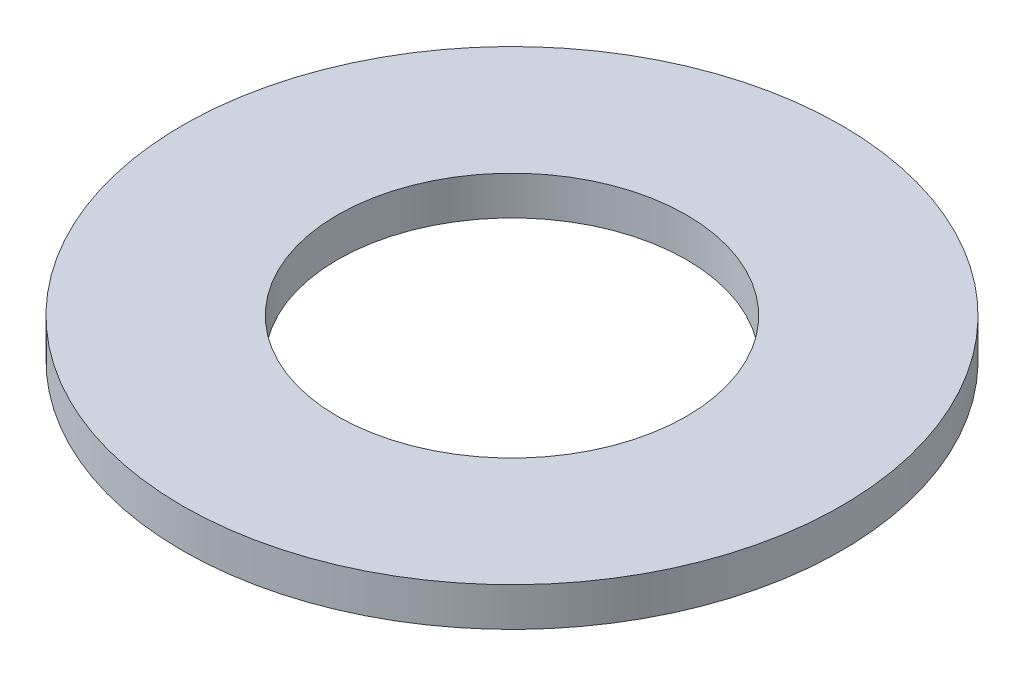
SolidWorks part; units mm, degrees
ref_plane "Front Plane" through (0, 0, 0) normal (0, 0, 1) x (1, 0, 0)
ref_plane "Top Plane" through (0, 0, 0) normal (0, 1, 0) x (1, 0, 0)
ref_plane "Right Plane" through (0, 0, 0) normal (1, 0, 0) x (0, 0, -1)
sketch "Sketch1" plane through (0, 0, 0) normal (0, 1, 0) x (1, 0, 0)
  circle A0 centre (0, 0) radius 85
  dimension "FLANGE_OD" = 170
extrude "Boss-Extrude1" add sketch "Sketch1" along normal blind 10
sketch "Sketch2" plane through (0, 0, 0) normal (0, 1, 0) x (1, 0, 0)
  circle A0 centre (0, 0) radius 45
  dimension "BORE_D" = 90
extrude "Cut-Extrude1" cut sketch "Sketch2" along normal through all
sketch "Sketch3" plane through (0, 10, 0) normal (0, 1, 0) x (1, 0, 0)
  circle A0 centre (0, 0) radius 40.4865 construction
  circle A1 centre (-40.4865, 0) radius 2.1431
  dimension "BOLT_D" = 4.2862
  dimension "BOLT_PCD" = 80.9729
extrude "Cut-Extrude2" cut sketch "Sketch3" against normal blind 9.5331 rebuild error yes
pattern_circular "CirPattern1" count 3 over 360 rebuild error yes
